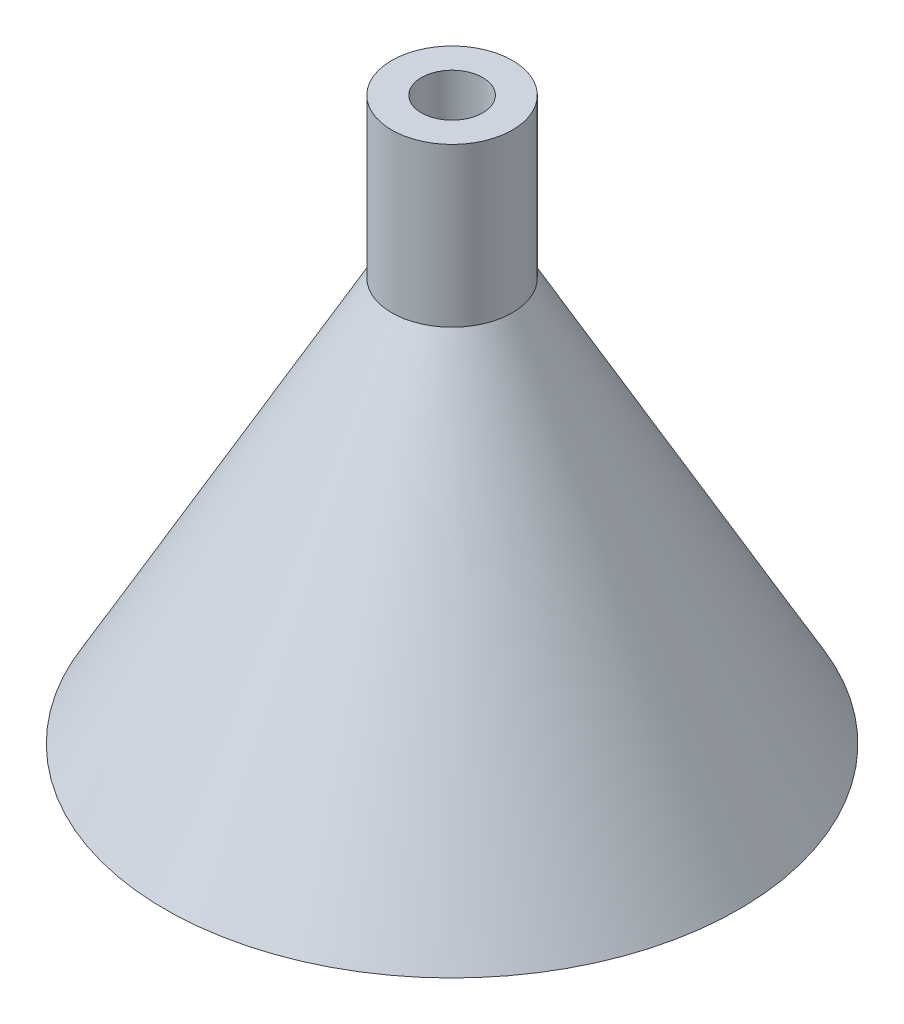
SolidWorks part; units mm, degrees
ref_plane "Front Plane" through (0, 0, 0) normal (0, 0, 1) x (1, 0, 0)
ref_plane "Top Plane" through (0, 0, 0) normal (0, 1, 0) x (1, 0, 0)
ref_plane "Right Plane" through (0, 0, 0) normal (1, 0, 0) x (0, 0, -1)
sketch "Sketch2" plane through (0, 0, 0) normal (0, 0, 1) x (1, 0, 0)
  line L0 (22.1177, 0) -> (29, 0)
  line L1 (29, 0) -> (6.096, 40.7622)
  line L2 (6.096, 40.7622) -> (6.096, 56.7622)
  line L3 (6.096, 56.7622) -> (3.096, 56.7622)
  line L4 (3.096, 56.7622) -> (3.096, 33.8529)
  line L5 (3.096, 33.8529) -> (22.1177, 0)
  line L6 (0, 0) -> (0, 50000) construction
  line L7 (-3.096, 33.8529) -> (-22.1177, 0) construction
  line L8 (-3.096, 56.7622) -> (-3.096, 33.8529) construction
  line L9 (-6.096, 56.7622) -> (-3.096, 56.7622) construction
  line L10 (-6.096, 40.7622) -> (-6.096, 56.7622) construction
  line L11 (-29, 0) -> (-6.096, 40.7622) construction
  line L12 (-22.1177, 0) -> (-29, 0) construction
  dimension "D1" = 3
  dimension "D2" = 6
  dimension "D3" = 12.192
  dimension "D4" = 58
  dimension "D5" = 16
revolve "Revolve1" add sketch "Sketch2" angle 360 about L6
